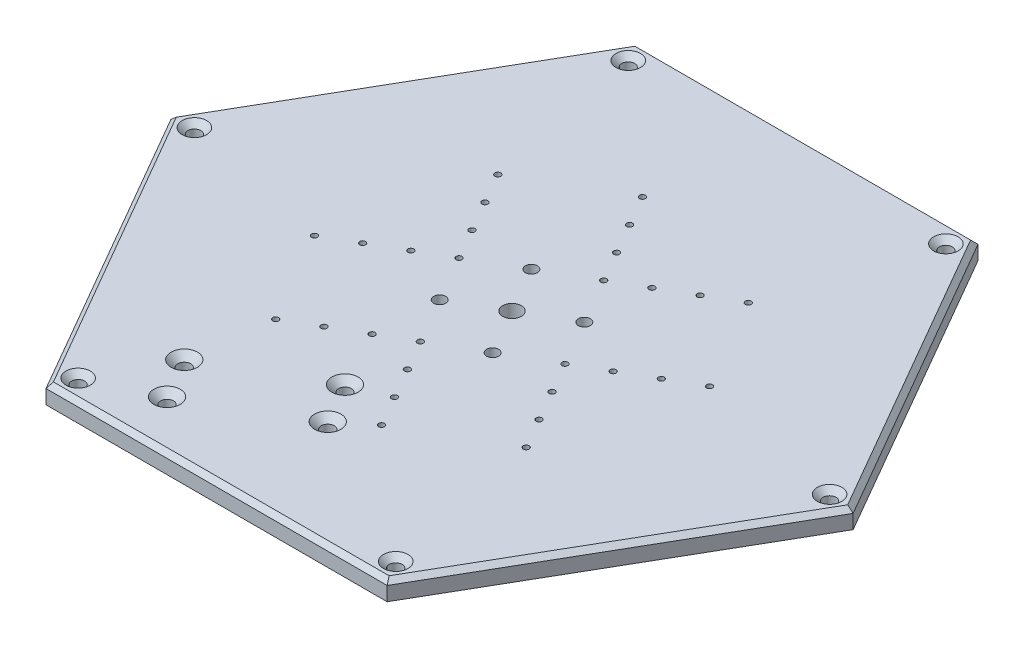
SolidWorks part; units mm, degrees
material "5052-H32"
ref_plane "Front Plane" through (0, 0, 0) normal (0, 0, 1) x (1, 0, 0)
ref_plane "Top Plane" through (0, 0, 0) normal (0, 1, 0) x (1, 0, 0)
ref_plane "Right Plane" through (0, 0, 0) normal (1, 0, 0) x (0, 0, -1)
sketch "Sketch1" plane through (0, 0, 0) normal (0, 1, 0) x (1, 0, 0)
  line L1 (72.5, 125.5737) -> (-72.5, 125.5737)
  line L2 (-72.5, 125.5737) -> (-145, 0)
  line L3 (-145, 0) -> (-72.5, -125.5737)
  line L4 (-72.5, -125.5737) -> (72.5, -125.5737)
  line L5 (72.5, -125.5737) -> (145, 0)
  line L6 (145, 0) -> (72.5, 125.5737)
  circle A0 centre (0, 0) radius 125.5737 construction
  dimension "D1" = 145
extrude "Boss-Extrude1" add sketch "Sketch1" along normal blind 8
sketch "Sketch10" plane through (0, 8, 0) normal (0, 1, 0) x (1, 0, 0)
  line L0 (145, 0) -> (0, 0) construction
  point P4 (135, 0)
  point P7 (67.5, -116.9134)
  point P8 (-67.5, -116.9134)
  point P9 (-135, 0)
  point P10 (-67.5, 116.9134)
  point P11 (67.5, 116.9134)
  point P12 (0, 0)
  dimension "D2" = 10
  dimension "D1" = 6
hole_wizard "CSK for M5 Flat Head Machine Screw2" positions "Sketch14" profile "Sketch13" countersink size "M5" standard "ANSI Metric"
sketch "Sketch14" plane through (0, 8, 0) normal (0, 1, 0) x (1, 0, 0)
  point P0 (-135, 0)
  point P3 (-67.5, -116.9134)
  point P6 (67.5, -116.9134)
  point P9 (135, 0)
  point P12 (67.5, 116.9134)
  point P15 (-67.5, 116.9134)
sketch "Sketch13" plane through (-135, 8, 0) normal (1, 0, 0) x (0, 0, 1)
  line L0 (0, 0) -> (0, 11.6524)
  line L1 (0, 11.6524) -> (2.75, 10)
  line L2 (2.75, 10) -> (2.75, 2.45)
  line L3 (2.75, 2.45) -> (5.2, 0)
  line L5 (5.2, 0) -> (0, 0)
  line L6 (-2.75, 2.45) -> (-5.2, 0) construction
  line L10 (0, 11.6524) -> (-2.75, 10) construction
  line L11 (0, -6.35) -> (0, 107.95) construction
  dimension "Hole Dia." = 5.5
  dimension "Hole Depth" = 10
  dimension "Near C'Sink Dia." = 10.4
  dimension "Near C'Sink Angle" = 90
  dimension "Drill Angle" = 118
chamfer "Chamfer4" distance 2 angle 45 6 edges at (0, 8, 125.5737) (108.75, 8, 62.7868) (108.75, 8, -62.7868) (0, 8, -125.5737) (-108.75, 8, -62.7868) (-108.75, 8, 62.7868)
sketch "Sketch15" plane through (0, 8, 0) normal (0, 1, 0) x (1, 0, 0)
  line L0 (0, 0) -> (107.0179, 61.7868) construction
  line L1 (142.6906, 0) -> (71.3453, 123.5737) construction
  line L2 (-30.7356, 8.2356) -> (-8.2356, -30.7356) construction
  line L3 (-30.7356, 8.2356) -> (8.2356, 30.7356) construction
  line L4 (-8.2356, -30.7356) -> (30.7356, -8.2356) construction
  line L5 (8.2356, 30.7356) -> (30.7356, -8.2356) construction
  line L6 (21.226, 38.2356) -> (43.726, -0.7356) construction
  line L7 (-11.25, 19.4856) -> (11.25, -19.4856) construction
  line L8 (34.2163, 45.7356) -> (56.7163, 6.7644) construction
  line L10 (47.2067, 53.2356) -> (69.7067, 14.2644) construction
  circle A0 centre (8.2356, 30.7356) radius 1.6 construction
  circle A1 centre (30.7356, -8.2356) radius 1.6 construction
  circle A2 centre (-8.2356, -30.7356) radius 1.6 construction
  circle A3 centre (-30.7356, 8.2356) radius 1.6 construction
  circle A4 centre (21.226, 38.2356) radius 1.6 construction
  circle A5 centre (43.726, -0.7356) radius 1.6 construction
  circle A6 centre (34.2163, 45.7356) radius 1.6 construction
  circle A7 centre (47.2067, 53.2356) radius 1.6 construction
  circle A8 centre (69.7067, 14.2644) radius 1.6 construction
  circle A9 centre (56.7163, 6.7644) radius 1.6 construction
  circle A10 centre (38.2356, -21.226) radius 1.6 construction
  circle A11 centre (45.7356, -34.2163) radius 1.6 construction
  circle A12 centre (53.2356, -47.2067) radius 1.6 construction
  circle A13 centre (14.2644, -69.7067) radius 1.6 construction
  circle A14 centre (6.7644, -56.7163) radius 1.6 construction
  circle A15 centre (-0.7356, -43.726) radius 1.6 construction
  circle A16 centre (-21.226, -38.2356) radius 1.6 construction
  circle A17 centre (-34.2163, -45.7356) radius 1.6 construction
  circle A18 centre (-47.2067, -53.2356) radius 1.6 construction
  circle A19 centre (-69.7067, -14.2644) radius 1.6 construction
  circle A20 centre (-56.7163, -6.7644) radius 1.6 construction
  circle A21 centre (-43.726, 0.7356) radius 1.6 construction
  circle A22 centre (-38.2356, 21.226) radius 1.6 construction
  circle A23 centre (-45.7356, 34.2163) radius 1.6 construction
  circle A24 centre (-53.2356, 47.2067) radius 1.6 construction
  circle A25 centre (-14.2644, 69.7067) radius 1.6 construction
  circle A26 centre (-6.7644, 56.7163) radius 1.6 construction
  circle A27 centre (0.7356, 43.726) radius 1.6 construction
  circle A28 centre (0, 0) radius 4.7625 construction
  circle A29 centre (19.4856, 11.25) radius 3.175 construction
  circle A30 centre (11.25, -19.4856) radius 3.175 construction
  circle A31 centre (-19.4856, -11.25) radius 3.175 construction
  circle A32 centre (-11.25, 19.4856) radius 3.175 construction
  point P16 (32.476, 18.75)
  point P18 (21.226, 38.2356)
  point P19 (43.726, -0.7356)
  point P23 (45.4663, 26.25)
  point P26 (58.4567, 33.75)
  point P71 (0, 0)
  point P81 (0, 0)
  dimension "D2" = 3.2
  dimension "D3" = 15
  dimension "D7" = 6.35
  dimension "D8" = 9.525
  dimension "D1" = 45
  dimension "D4" = 15
  dimension "D5" = 15
  dimension "D6" = 4
  dimension "D9" = 4
sketch "Sketch19" plane through (0, 8, 0) normal (0, -1, 0) x (1, 0, 0)
  line L0 (1.5942, 79.9086) -> (-41.7071, 104.9086) construction
  line L1 (-41.7071, 104.9086) -> (-51.7071, 87.5881) construction
  line L2 (-51.7071, 87.5881) -> (-8.4058, 62.5881) construction
  line L3 (-8.4058, 62.5881) -> (1.5942, 79.9086) construction
  line L4 (-20.0564, 92.4086) -> (-25.0564, 83.7484) construction
  line L5 (-25.0564, 83.7484) -> (-3.4058, 71.2484) construction
  line L6 (-25.0564, 83.7484) -> (-78.75, 114.7484) construction
  line L7 (-145, 0) -> (-72.5, 125.5737) construction
  dimension "D1" = 50
  dimension "D2" = 20
  dimension "D3" = 62
  dimension "D4" = 12.5
hole_wizard "CSK for M5 SFHCS1" positions "Sketch21" profile "Sketch22" countersink size "M5" standard "ANSI Metric"
sketch "Sketch21" plane through (0, 8, 0) normal (0, 1, 0) x (1, 0, 0)
  point P0 (1.5942, -79.9086)
  point P3 (-8.4058, -62.5881)
  point P6 (-51.7071, -87.5881)
  point P9 (-41.7071, -104.9086)
sketch "Sketch22" plane through (1.5942, 8, 79.9086) normal (1, 0, 0) x (0, 0, 1)
  line L0 (0, 0) -> (0, 11.6524)
  line L1 (0, 11.6524) -> (2.75, 10)
  line L2 (2.75, 10) -> (2.75, 2.85)
  line L3 (2.75, 2.85) -> (5.6, 0)
  line L5 (5.6, 0) -> (0, 0)
  line L6 (-2.75, 2.85) -> (-5.6, 0) construction
  line L10 (0, 11.6524) -> (-2.75, 10) construction
  line L11 (0, -6.35) -> (0, 107.95) construction
  dimension "Hole Dia." = 5.5
  dimension "Hole Depth" = 10
  dimension "Near C'Sink Dia." = 11.2
  dimension "Near C'Sink Angle" = 90
  dimension "Drill Angle" = 118
hole_wizard "M3x0.5 Tapped Hole1" positions "Sketch24" profile "Sketch23" tap size "M3x0.5" standard "ANSI Metric" end condition through all
sketch "Sketch24" plane through (0, 8, 0) normal (0, 1, 0) x (1, 0, 0)
  point P0 (47.2067, 53.2356)
  point P3 (69.7067, 14.2644)
  point P6 (56.7163, 6.7644)
  point P9 (34.2163, 45.7356)
  point P12 (21.226, 38.2356)
  point P15 (43.726, -0.7356)
  point P18 (38.2356, -21.226)
  point P21 (45.7356, -34.2163)
  point P24 (53.2356, -47.2067)
  point P27 (14.2644, -69.7067)
  point P30 (6.7644, -56.7163)
  point P33 (-0.7356, -43.726)
  point P36 (-8.2356, -30.7356)
  point P39 (-30.7356, 8.2356)
  point P42 (8.2356, 30.7356)
  point P45 (30.7356, -8.2356)
  point P48 (0.7356, 43.726)
  point P51 (-6.7644, 56.7163)
  point P54 (-14.2644, 69.7067)
  point P57 (-53.2356, 47.2067)
  point P60 (-45.7356, 34.2163)
  point P63 (-38.2356, 21.226)
  point P66 (-43.726, 0.7356)
  point P69 (-56.7163, -6.7644)
  point P72 (-69.7067, -14.2644)
  point P75 (-47.2067, -53.2356)
  point P78 (-34.2163, -45.7356)
  point P81 (-21.226, -38.2356)
sketch "Sketch23" plane through (47.2067, 8, -53.2356) normal (1, 0, 0) x (0, 0, 1)
  line L0 (0, 0) -> (0, 8)
  line L1 (0, 8) -> (1.25, 8)
  line L2 (1.25, 8) -> (1.25, 0)
  line L5 (1.25, 0) -> (0, 0)
  line L11 (0, -6.35) -> (0, 107.95) construction
  dimension "Thru Tap Drill Dia." = 2.5
  dimension "Thru Tap Drill Depth" = 8
cosmetic thread "Hole Thread1" parameters "D2"=3
cosmetic thread "Hole Thread2" parameters "D2"=3
cosmetic thread "Hole Thread3" parameters "D2"=3
cosmetic thread "Hole Thread4" parameters "D2"=3
cosmetic thread "Hole Thread5" parameters "D2"=3
cosmetic thread "Hole Thread6" parameters "D2"=3
cosmetic thread "Hole Thread7" parameters "D2"=3
cosmetic thread "Hole Thread8" parameters "D2"=3
cosmetic thread "Hole Thread9" parameters "D2"=3
cosmetic thread "Hole Thread10" parameters "D2"=3
cosmetic thread "Hole Thread11" parameters "D2"=3
cosmetic thread "Hole Thread12" parameters "D2"=3
cosmetic thread "Hole Thread13" parameters "D2"=3
cosmetic thread "Hole Thread14" parameters "D2"=3
cosmetic thread "Hole Thread15" parameters "D2"=3
cosmetic thread "Hole Thread16" parameters "D2"=3
cosmetic thread "Hole Thread17" parameters "D2"=3
cosmetic thread "Hole Thread18" parameters "D2"=3
cosmetic thread "Hole Thread19" parameters "D2"=3
cosmetic thread "Hole Thread20" parameters "D2"=3
cosmetic thread "Hole Thread21" parameters "D2"=3
cosmetic thread "Hole Thread22" parameters "D2"=3
cosmetic thread "Hole Thread23" parameters "D2"=3
cosmetic thread "Hole Thread24" parameters "D2"=3
cosmetic thread "Hole Thread25" parameters "D2"=3
cosmetic thread "Hole Thread26" parameters "D2"=3
cosmetic thread "Hole Thread27" parameters "D2"=3
cosmetic thread "Hole Thread28" parameters "D2"=3
hole_wizard "1/4-20 Tapped Hole1" positions "Sketch26" profile "Sketch25" tap size "1/4-20" standard "ANSI Inch" end condition through all
sketch "Sketch26" plane through (0, 8, 0) normal (0, 1, 0) x (1, 0, 0)
  point P0 (19.4856, 11.25)
  point P3 (-11.25, 19.4856)
  point P6 (-19.4856, -11.25)
  point P9 (11.25, -19.4856)
sketch "Sketch25" plane through (19.4856, 8, -11.25) normal (1, 0, 0) x (0, 0, 1)
  line L0 (0, 0) -> (0, 8)
  line L1 (0, 8) -> (2.5527, 8)
  line L2 (2.5527, 8) -> (2.5527, 0)
  line L5 (2.5527, 0) -> (0, 0)
  line L11 (0, -6.35) -> (0, 107.95) construction
  dimension "Thru Tap Drill Dia." = 5.1054
  dimension "Thru Tap Drill Depth" = 8
cosmetic thread "Hole Thread29" parameters "D2"=6.35
cosmetic thread "Hole Thread30" parameters "D2"=6.35
cosmetic thread "Hole Thread31" parameters "D2"=6.35
cosmetic thread "Hole Thread32" parameters "D2"=6.35
hole_wizard "3/8-16 Tapped Hole1" positions "Sketch28" profile "Sketch27" tap size "3/8-16" standard "ANSI Inch" end condition through all
sketch "Sketch28" plane through (0, 8, 0) normal (0, 1, 0) x (1, 0, 0)
  point P0 (0, 0)
sketch "Sketch27" plane through (0, 8, 0) normal (1, 0, 0) x (0, 0, 1)
  line L0 (0, 0) -> (0, 8)
  line L1 (0, 8) -> (3.9687, 8)
  line L2 (3.9687, 8) -> (3.9687, 0)
  line L5 (3.9687, 0) -> (0, 0)
  line L11 (0, -6.35) -> (0, 107.95) construction
  dimension "Thru Tap Drill Dia." = 7.9375
  dimension "Thru Tap Drill Depth" = 8
cosmetic thread "Hole Thread33" parameters "D2"=9.525
